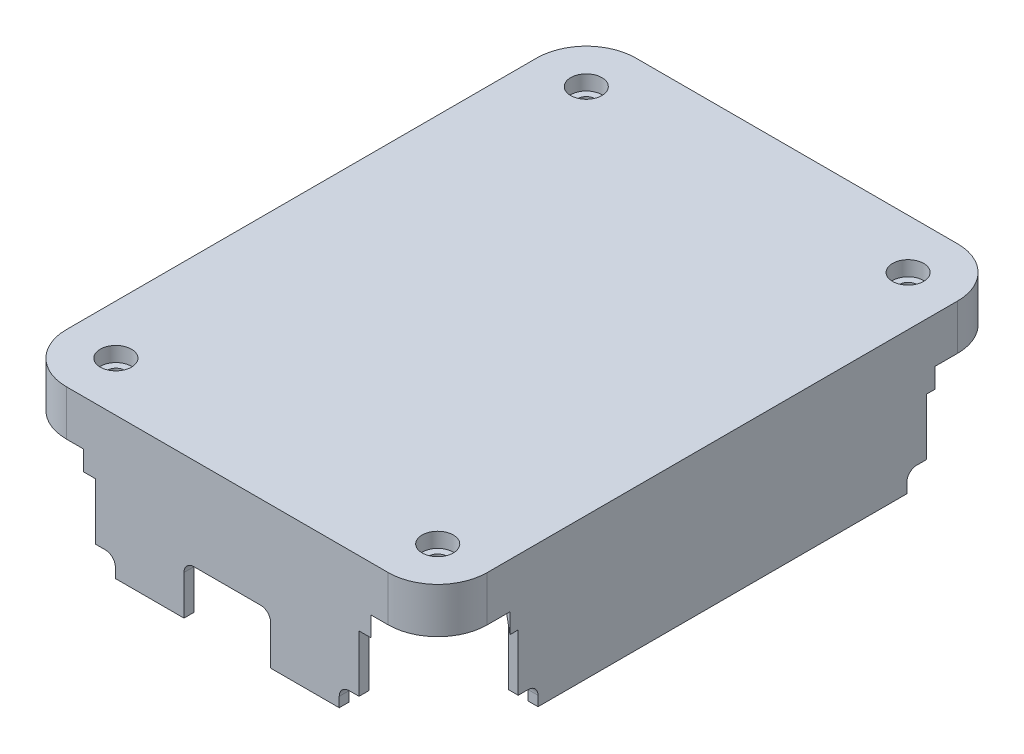
SolidWorks part; units mm, degrees
note: '?' marks a value the reader was unsure of.
material "3-D Printed ABS"
ref_plane "Front Plane" through (0, 0, 0) normal (0, 0, 1) x (1, 0, 0)
ref_plane "Top Plane" through (0, 0, 0) normal (0, 1, 0) x (1, 0, 0)
ref_plane "Right Plane" through (0, 0, 0) normal (1, 0, 0) x (0, 0, -1)
sketch "Sketch1" plane through (0, 0, 0) normal (0, 1, 0) x (1, 0, 0)
  line L1 (-53.975, -73.025) -> (53.975, -73.025)
  line L2 (-53.975, -73.025) -> (-53.975, 73.025)
  line L3 (-53.975, 73.025) -> (53.975, 73.025)
  line L4 (53.975, -73.025) -> (53.975, 73.025)
  line L5 (-53.975, -73.025) -> (53.975, 73.025) construction
  line L6 (-53.975, 73.025) -> (53.975, -73.025) construction
  point P0 (0, 0)
  dimension "D1" = 107.95
  dimension "D2" = 146.05
extrude "Boss-Extrude1" add sketch "Sketch1" against normal blind 2.54
sketch "Sketch13" plane through (0, 0, 0) normal (0, 1, 0) x (1, 0, 0)
  line L0 (0, 155.0212) -> (0, -155.0212) construction
  line L1 (0, 0) -> (-92.0171, 0) construction
  line L2 (53.975, -73.025) -> (53.975, 73.025) construction
  line L3 (53.975, -73.025) -> (28.575, -73.025)
  line L4 (53.975, -73.025) -> (53.975, -47.625)
  line L5 (53.975, -47.625) -> (28.575, -47.625)
  line L6 (28.575, -73.025) -> (28.575, -47.625)
  line L7 (-53.975, -73.025) -> (53.975, -73.025) construction
  line L8 (-28.575, -73.025) -> (-28.575, -47.625)
  line L9 (-53.975, -47.625) -> (-28.575, -47.625)
  line L10 (-53.975, -73.025) -> (-53.975, -47.625)
  line L11 (-53.975, -73.025) -> (-28.575, -73.025)
  line L12 (-53.975, 73.025) -> (-28.575, 73.025)
  line L13 (-53.975, 73.025) -> (-53.975, 47.625)
  line L14 (-53.975, 47.625) -> (-28.575, 47.625)
  line L15 (-28.575, 73.025) -> (-28.575, 47.625)
  line L16 (28.575, 73.025) -> (28.575, 47.625)
  line L17 (53.975, 47.625) -> (28.575, 47.625)
  line L18 (53.975, 73.025) -> (53.975, 47.625)
  line L19 (53.975, 73.025) -> (28.575, 73.025)
  dimension "D1" = 25.4
  dimension "D2" = 25.4
extrude "Boss-Extrude4" add sketch "Sketch13" against normal blind 16.7107
sketch "Sketch2" plane through (0, 0, 0) normal (0, 1, 0) x (1, 0, 0)
  line L0 (0, 0) -> (100.1618, 0) construction
  line L1 (0, 0) -> (0, 86.3534) construction
  line L2 (-53.975, 73.025) -> (-53.975, -73.025) construction
  line L3 (53.975, 73.025) -> (-53.975, 73.025) construction
  line L4 (0, 0) -> (-53.975, 73.025) construction
  circle A0 centre (-41.275, 60.325) radius 3.302
  circle A1 centre (41.275, 60.325) radius 3.302
  circle A2 centre (41.275, -60.325) radius 3.302
  circle A3 centre (-41.275, -60.325) radius 3.302
  dimension "D1" = 6.604
  dimension "D3" = 12.7
  dimension "D2" = 12.7
extrude "Cut-Extrude1" cut sketch "Sketch2" against normal through all
sketch "Sketch3" plane through (0, 0, 0) normal (0, 1, 0) x (1, 0, 0)
  line L0 (-53.975, 25.4) -> (53.975, 25.4) construction
  line L1 (-23.495, 60.325) -> (-19.05, 60.325)
  line L2 (-23.495, 60.325) -> (-23.495, 44.45)
  line L3 (-23.495, 44.45) -> (-19.05, 44.45)
  line L4 (-19.05, 60.325) -> (-19.05, 44.45)
  line L5 (19.05, 60.325) -> (19.05, 44.45)
  line L6 (23.495, 44.45) -> (19.05, 44.45)
  line L7 (23.495, 60.325) -> (23.495, 44.45)
  line L8 (23.495, 60.325) -> (19.05, 60.325)
  line L9 (-53.975, 73.025) -> (-53.975, -73.025) construction
  line L10 (53.975, -73.025) -> (53.975, 73.025) construction
  line L11 (0, 0) -> (0, 97.7255) construction
  line L12 (0, 50.8) -> (0, -46.9255) construction
  line L13 (23.495, -9.525) -> (19.05, -9.525)
  line L14 (23.495, -9.525) -> (23.495, 6.35)
  line L15 (23.495, 6.35) -> (19.05, 6.35)
  line L16 (19.05, -9.525) -> (19.05, 6.35)
  line L17 (-19.05, -9.525) -> (-19.05, 6.35)
  line L18 (-23.495, 6.35) -> (-19.05, 6.35)
  line L19 (-23.495, -9.525) -> (-23.495, 6.35)
  line L20 (-23.495, -9.525) -> (-19.05, -9.525)
  dimension "D1" = 15.875
  dimension "D2" = 4.445
  dimension "D3" = 19.05
  dimension "D4" = 25.4
  dimension "D5" = 44.45
extrude "Cut-Extrude2" [suppressed] cut sketch "Sketch3" against normal through all
fillet "Fillet1" radius 12.7 4 edges at (53.975, -8.3553, -73.025) (53.975, -8.3553, 73.025) (-53.975, -8.3553, 73.025) (-53.975, -8.3553, -73.025)
sketch "Sketch4" plane through (0, 0, 0) normal (0, 1, 0) x (1, 0, 0)
  line L0 (0, 0) -> (80.9727, -80.9727) construction
  line L1 (0, 0) -> (-80.9727, -80.9727) construction
  line L2 (69.1118, -51.1513) -> (28.7006, -10.7401)
  line L3 (28.7006, -10.7401) -> (10.7401, -28.7006)
  line L4 (10.7401, -28.7006) -> (51.1513, -69.1118)
  line L5 (51.1513, -69.1118) -> (69.1118, -51.1513)
  line L6 (0, 0) -> (0, -118.7381) construction
  line L7 (0, 0) -> (-98.4177, 0) construction
  line L8 (-51.1513, -69.1118) -> (-69.1118, -51.1513)
  line L9 (-69.1118, -51.1513) -> (-28.7006, -10.7401)
  line L10 (-28.7006, -10.7401) -> (-10.7401, -28.7006)
  line L11 (-10.7401, -28.7006) -> (-51.1513, -69.1118)
  line L12 (-69.1118, 51.1513) -> (-28.7006, 10.7401)
  line L13 (-51.1513, 69.1118) -> (-69.1118, 51.1513)
  line L14 (-10.7401, 28.7006) -> (-51.1513, 69.1118)
  line L15 (-28.7006, 10.7401) -> (-10.7401, 28.7006)
  line L16 (51.1513, 69.1118) -> (69.1118, 51.1513)
  line L17 (69.1118, 51.1513) -> (28.7006, 10.7401)
  line L18 (28.7006, 10.7401) -> (10.7401, 28.7006)
  line L19 (10.7401, 28.7006) -> (51.1513, 69.1118)
  point P6 (19.7204, -19.7204)
  dimension "D1" = 25.4
  dimension "D2" = 57.15
  dimension "D3" = 45
extrude "Cut-Extrude3" [suppressed] cut sketch "Sketch4" against normal blind 1.5875
sketch "Sketch6" [suppressed] plane through (0, 0, 0) normal (0, 1, 0) x (1, 0, 0)
  line L0 (46.3377, -44.1074) -> (34.6634, -32.4331) construction
  line L1 (0, 0) -> (0, -117.7376) construction
  line L2 (0, 0) -> (-151.7285, 0) construction
  line L4 (28.1601, -10.1996) -> (10.1996, -28.1601) construction
  line L5 (50.6107, -68.5712) -> (68.5712, -50.6107) construction
  text T0 "ESC" font "Century Gothic" height in points 22
  dimension "D1" = 45
  dimension "D2" = 20.32
  dimension "D3" = 20.32
extrude "Cut-Extrude5" [suppressed] cut sketch "Sketch6" against normal blind 3.175
sketch "Sketch5" plane through (0, 0, 0) normal (0, 1, 0) x (1, 0, 0)
  line L0 (41.275, 73.025) -> (-41.275, 73.025) construction
  line L1 (14.2875, 15.875) -> (-14.2875, 15.875)
  line L2 (14.2875, 15.875) -> (14.2875, 66.675)
  line L3 (14.2875, 66.675) -> (-14.2875, 66.675)
  line L4 (-14.2875, 15.875) -> (-14.2875, 66.675)
  point P4 (0, 15.875)
  dimension "D1" = 50.8
  dimension "D2" = 28.575
  dimension "D3" = 6.35
extrude "Cut-Extrude4" [suppressed] cut sketch "Sketch5" against normal blind 1.5875
ref_axis "Axis1" through (0, 0.3175, 0) along (0, -1, 0)?
pattern_circular "CirPattern1" [suppressed] count 4 over 360 about axis through (0, 0.3175, 0) along (0, -1, 0)
sketch "Sketch7" plane through (0, 0, 0) normal (0, 1, 0) x (1, 0, 0)
  line L0 (0, 0) -> (0, -54.962) construction
  line L1 (63.4018, -13.3522) -> (38.0018, -13.3522)
  line L2 (63.4018, -13.3522) -> (63.4018, 43.7978)
  line L3 (63.4018, 43.7978) -> (38.0018, 43.7978)
  line L4 (38.0018, -13.3522) -> (38.0018, 43.7978)
  line L5 (-38.0018, -13.3522) -> (-38.0018, 43.7978)
  line L6 (-63.4018, 43.7978) -> (-38.0018, 43.7978)
  line L7 (-63.4018, -13.3522) -> (-63.4018, 43.7978)
  line L8 (-63.4018, -13.3522) -> (-38.0018, -13.3522)
  line L9 (-41.275, -73.025) -> (41.275, -73.025) construction
  line L10 (38.5677, -40.64) -> (-18.5823, -40.64)
  line L11 (38.5677, -40.64) -> (38.5677, -66.04)
  line L12 (38.5677, -66.04) -> (-18.5823, -66.04)
  line L13 (-18.5823, -40.64) -> (-18.5823, -66.04)
  line L14 (38.5677, -40.64) -> (-18.5823, -66.04) construction
  line L15 (38.5677, -66.04) -> (-18.5823, -40.64) construction
  line L16 (19.844, -36.1003) -> (-37.306, -36.1003)
  line L17 (19.844, -36.1003) -> (19.844, -61.5003)
  line L18 (19.844, -61.5003) -> (-37.306, -61.5003)
  line L19 (-37.306, -36.1003) -> (-37.306, -61.5003)
  line L20 (19.844, -36.1003) -> (-37.306, -61.5003) construction
  line L21 (19.844, -61.5003) -> (-37.306, -36.1003) construction
  point P11 (9.9927, -53.34)
  point P18 (-8.731, -48.8003)
  dimension "D1" = 57.15
  dimension "D2" = 25.4
  dimension "D3" = 57.15
  dimension "D4" = 25.4
  dimension "D5" = 6.985
  dimension "D6" = 57.15
  dimension "D7" = 25.4
extrude "Cut-Extrude6" [suppressed] cut sketch "Sketch7" against normal blind 1.27
sketch "Sketch8" plane through (0, 0, 0) normal (0, 1, 0) x (1, 0, 0)
  line L7 (19.05, -31.75) -> (-19.05, -31.75)
  line L8 (19.05, -31.75) -> (19.05, 31.75)
  line L9 (19.05, 31.75) -> (-19.05, 31.75)
  line L10 (-19.05, -31.75) -> (-19.05, 31.75)
  point P0 (0, 0)
  dimension "D1" = 38.1
  dimension "D2" = 31.75
  dimension "D3" = 63.5
extrude "Boss-Extrude3" [suppressed] add sketch "Sketch8" along normal blind 2.54
sketch "Sketch11" plane through (0, 0, 0) normal (0, 1, 0) x (1, 0, 0)
  line L1 (19.05, -9.525) -> (-19.05, -9.525)
  line L2 (19.05, -9.525) -> (19.05, 6.35)
  line L3 (19.05, 6.35) -> (-19.05, 6.35)
  line L4 (-19.05, -9.525) -> (-19.05, 6.35)
extrude "Cut-Extrude9" [suppressed] cut sketch "Sketch11" against normal mid plane 2.54
sketch "Sketch12" [suppressed] plane through (0, 0, 0) normal (0, 1, 0) x (1, 0, 0)
  line L0 (-23.495, -9.525) -> (-19.05, -9.525) construction
  line L1 (12.7, -9.525) -> (-12.7, -9.525)
  line L2 (12.7, -9.525) -> (12.7, 6.35)
  line L3 (12.7, 6.35) -> (-12.7, 6.35)
  line L4 (-12.7, -9.525) -> (-12.7, 6.35)
  line L5 (-19.05, 6.35) -> (-23.495, 6.35) construction
  line L6 (19.05, 52.3875) -> (-19.05, 52.3875) construction
  line L7 (19.05, 60.325) -> (19.05, 44.45) construction
  line L8 (-19.05, 44.45) -> (-19.05, 60.325) construction
  line L9 (-12.7, 114.3) -> (-12.7, 98.425)
  line L10 (12.7, 98.425) -> (-12.7, 98.425)
  line L11 (12.7, 114.3) -> (12.7, 98.425)
  line L12 (12.7, 114.3) -> (-12.7, 114.3)
  point P8 (0, -9.525)
  dimension "D1" = 25.4
extrude "Cut-Extrude12" [suppressed] cut sketch "Sketch12" along normal through all
sketch "Sketch9" plane through (0, 0, 0) normal (0, 1, 0) x (1, 0, 0)
  line L1 (25.1579, -52.4084) -> (-25.6421, -52.4084)
  line L2 (25.1579, -52.4084) -> (25.1579, -1.6084)
  line L3 (25.1579, -1.6084) -> (-25.6421, -1.6084)
  line L4 (-25.6421, -52.4084) -> (-25.6421, -1.6084)
  line L5 (25.1579, -52.4084) -> (-25.6421, -1.6084) construction
  line L6 (25.1579, -1.6084) -> (-25.6421, -52.4084) construction
  point P0 (-0.2421, -27.0084)
  dimension "D1" = 50.8
  dimension "D2" = 50.8
fillet "Fillet2" [suppressed] radius 12.7
sketch "Sketch14" plane through (0, -16.7107, 0) normal (0, -1, 0) x (1, 0, 0)
  line L0 (0, 0) -> (0, -152.4) construction
  line L1 (0, 0) -> (152.4, 0) construction
  line L2 (0, 0) -> (152.4, -152.4) construction
  line L3 (152.4, -152.4) -> (41.275, -60.325) construction
  line L4 (41.275, -60.325) -> (28.7776, -49.97) construction
  line L5 (28.7776, -49.97) -> (0, -26.1257) construction
  line L6 (22.4276, -28.3459) -> (6.35, -47.7499)
  line L7 (6.35, -47.7499) -> (138.4692, -157.2201)
  line L8 (138.4692, -157.2201) -> (154.5468, -137.816)
  line L9 (154.5468, -137.816) -> (22.4276, -28.3459)
  line L10 (-22.4276, -28.3459) -> (-6.35, -47.7499)
  line L11 (-154.5468, -137.816) -> (-22.4276, -28.3459)
  line L12 (-6.35, -47.7499) -> (-138.4692, -157.2201)
  line L13 (-138.4692, -157.2201) -> (-154.5468, -137.816)
  line L14 (-154.5468, 137.816) -> (-22.4276, 28.3459)
  line L15 (-138.4692, 157.2201) -> (-154.5468, 137.816)
  line L16 (-6.35, 47.7499) -> (-138.4692, 157.2201)
  line L17 (-22.4276, 28.3459) -> (-6.35, 47.7499)
  line L18 (22.4276, 28.3459) -> (6.35, 47.7499)
  line L19 (138.4692, 157.2201) -> (154.5468, 137.816)
  line L20 (154.5468, 137.816) -> (22.4276, 28.3459)
  line L21 (6.35, 47.7499) -> (138.4692, 157.2201)
  point P3 (14.3888, -38.0479)
  point P6 (41.275, -60.325)
  dimension "D1" = 152.4
  dimension "D2" = 152.4
  dimension "D3" = 6.35
  dimension "D4" = 12.5997
extrude "Cut-Extrude13" cut sketch "Sketch14" against normal blind 5.08
sketch "Sketch15" plane through (0, 0, 0) normal (0, 1, 0) x (1, 0, 0)
  line L0 (0, 0) -> (72.5178, 0) construction
  line L1 (0, 0) -> (0, 124.598) construction
  circle A0 centre (-41.275, 60.325) radius 6.35
  circle A1 centre (41.275, 60.325) radius 6.35
  circle A2 centre (-41.275, -60.325) radius 6.35
  circle A3 centre (41.275, -60.325) radius 6.35
extrude "Boss-Extrude5" add sketch "Sketch15" against normal offset from surface (9.0907 mm away) 2.54 up to face at (-41.6508, -11.6307, -60.7008)
hole_wizard "M4 Clearance Hole1" [suppressed] positions "Sketch18" profile "Sketch16" hole size "M4" standard "ANSI Metric"
sketch "Sketch18" plane through (0, -19.05, 0) normal (0, -1, 0) x (-1, 0, 0)
  point P0 (41.275, 60.325)
  point P3 (41.275, -60.325)
  point P6 (-41.275, -60.325)
  point P9 (-41.275, 60.325)
sketch "Sketch16" plane through (-41.275, -19.05, -60.325) normal (1, 0, 0) x (0, 0, -1)
  line L0 (0, 0) -> (0, 19.05)
  line L1 (0, 19.05) -> (2.25, 19.05)
  line L2 (2.25, 19.05) -> (2.25, 0)
  line L5 (2.25, 0) -> (0, 0)
  line L11 (0, -6.35) -> (0, 107.95) construction
  dimension "Thru Hole Dia." = 4.5
  dimension "Thru Hole Depth" = 19.05
hole_wizard "CBORE for M4 SHCS1" [suppressed] positions "Sketch21" profile "Sketch20" counterbore size "M4" standard "ANSI Metric"
sketch "Sketch21" [suppressed] plane through (0, 0, 0) normal (0, 1, 0) x (1, 0, 0)
  point P0 (41.275, 60.325)
  point P3 (-41.275, 60.325)
  point P6 (-41.275, -60.325)
  point P9 (41.275, -60.325)
sketch "Sketch20" plane through (41.275, 0, -60.325) normal (1, 0, 0) x (0, 0, 1)
  line L0 (0, 0) -> (0, 24.13)
  line L1 (0, 24.13) -> (2.25, 24.13)
  line L3 (2.25, 24.13) -> (2.25, 4)
  line L4 (2.25, 4) -> (4, 4)
  line L5 (4, 4) -> (4, 0)
  line L7 (4, 0) -> (0, 0)
  line L11 (0, -6.35) -> (0, 107.95) construction
  dimension "Thru Hole Dia." = 4.5
  dimension "Thru Hole Depth" = 24.13
  dimension "C'Bore Dia." = 8
  dimension "C'Bore Depth" = 4
sketch "Sketch23" plane through (0, -11.6307, 0) normal (0, -1, 0) x (1, 0, 0)
  circle A0 centre (-41.275, -60.325) radius 2.25
  dimension "D1" = 4.5
extrude "Cut-Extrude14" cut sketch "Sketch23" against normal through all
sketch "Sketch24" plane through (0, 0, 0) normal (0, 1, 0) x (1, 0, 0)
  circle A0 centre (-41.275, 60.325) radius 4
  dimension "D1" = 8
extrude "Cut-Extrude15" cut sketch "Sketch24" against normal blind 3.81
mirror "Mirror1" about plane through (0, 0, 0) normal (0, 0, 1) of "Cut-Extrude15", "Cut-Extrude14"
mirror "Mirror2" about plane through (0, 0, 0) normal (1, 0, 0) of "Cut-Extrude15", "Cut-Extrude14", "Mirror1"
fillet "Fillet3" radius 12.7 4 edges at (-28.575, -7.0853, -47.625) (28.575, -7.0853, -47.625) (28.575, -7.0853, 47.625) (-28.575, -7.0853, 47.625)
sketch "Sketch25" plane through (0, 0, 0) normal (0, 1, 0) x (1, 0, 0)
  line L0 (0, 0) -> (0, -33.9706) construction
  line L1 (0, 0) -> (63.8751, 0) construction
  circle A0 centre (30.0609, 0) radius 3.4925
  circle A1 centre (30.0609, -24.9682) radius 3.4925
  circle A2 centre (30.0609, 24.9682) radius 3.4925
  circle A3 centre (-30.0609, 24.9682) radius 3.4925
  circle A4 centre (-30.0609, -24.9682) radius 3.4925
  circle A5 centre (-30.0609, 0) radius 3.4925
  dimension "D1" = 6.985
  dimension "D2" = 6.985
  dimension "D3" = 24.9682
  dimension "D4" = 30.0609
extrude "GimbalMount1" [suppressed] cut sketch "Sketch25" against normal through all
sketch "Sketch26" [suppressed] plane through (0, 0, 0) normal (0, 1, 0) x (1, 0, 0)
  circle A0 centre (30.0609, -24.9682) radius 5.715
  circle A1 centre (30.0609, 0) radius 5.715
  circle A2 centre (30.0609, 24.9682) radius 5.715
  circle A3 centre (-30.0609, -24.9682) radius 5.715
  circle A4 centre (-30.0609, 0) radius 5.715
  circle A5 centre (-30.0609, 24.9682) radius 5.715
  dimension "D1" = 11.43
extrude "GimbalMount2" [suppressed] cut sketch "Sketch26" against normal blind 1.524
fillet "Fillet4" radius 1.016 4 edges at (41.275, -11.6307, 63.627) (-41.275, -11.6307, 57.023) (-41.275, -11.6307, -57.023) (41.275, -11.6307, -63.627)
sketch "Sketch27" plane through (0, -2.54, 0) normal (0, -1, 0) x (1, 0, 0)
  line L1 (33.7889, -73.025) -> (-33.7889, -73.025)
  line L2 (33.7889, -73.025) -> (33.7889, -70.485)
  line L3 (33.7889, -70.485) -> (-33.7889, -70.485)
  line L4 (-33.7889, -73.025) -> (-33.7889, -70.485)
  line L6 (0, 0) -> (0, -45.0707) construction
  line L7 (0, 0) -> (-77.1364, 0) construction
  line L8 (-33.7889, 73.025) -> (-33.7889, 70.485)
  line L9 (33.7889, 70.485) -> (-33.7889, 70.485)
  line L10 (33.7889, 73.025) -> (33.7889, 70.485)
  line L11 (33.7889, 73.025) -> (-33.7889, 73.025)
  line L13 (53.975, -52.3805) -> (51.435, -52.3805)
  line L14 (53.975, -52.3805) -> (53.975, 52.3805)
  line L15 (53.975, 52.3805) -> (51.435, 52.3805)
  line L16 (51.435, -52.3805) -> (51.435, 52.3805)
  line L17 (-51.435, -52.3805) -> (-51.435, 52.3805)
  line L18 (-53.975, 52.3805) -> (-51.435, 52.3805)
  line L19 (-53.975, -52.3805) -> (-53.975, 52.3805)
  line L20 (-53.975, -52.3805) -> (-51.435, -52.3805)
  line L22 (28.575, -66.1649) -> (36.8544, -73.025) construction
  line L23 (-36.8544, -73.025) -> (-28.575, -66.1649) construction
  line L24 (28.575, -73.025) -> (-28.575, -73.025) construction
  line L25 (53.975, -54.4851) -> (45.6956, -47.625) construction
  line L26 (53.975, 47.625) -> (53.975, -47.625) construction
  line L27 (45.6956, 47.625) -> (53.975, 54.4851) construction
  dimension "D1" = 2.54
  dimension "D2" = 2.54
extrude "Boss-Extrude6" add sketch "Sketch27" along normal blind 33.782
sketch "Sketch28" plane through (0, 0, -73.025) normal (0, 0, -1) x (-1, 0, 0)
  line L0 (-41.275, 0) -> (41.275, 0) construction
  line L1 (-17.526, -36.322) -> (17.526, -36.322)
  line L2 (-16.891, -28.702) -> (-16.891, -21.3995)
  line L3 (-14.351, -18.8595) -> (14.351, -18.8595)
  line L4 (16.891, -28.702) -> (16.891, -21.3995)
  line L5 (33.7889, -36.322) -> (-33.7889, -36.322) construction
  line L6 (19.431, -31.242) -> (27.051, -31.242)
  line L7 (0, -18.8595) -> (0, 0) construction
  line L8 (17.526, -36.322) -> (29.591, -36.322)
  line L9 (29.591, -33.782) -> (29.591, -36.322)
  line L11 (-19.431, -31.242) -> (-27.051, -31.242)
  line L13 (-17.526, -36.322) -> (-29.591, -36.322)
  line L14 (-29.591, -33.782) -> (-29.591, -36.322)
  arc A0 (-29.591, -33.782) -> (-27.051, -31.242) centre (-27.051, -33.782) cw
  arc A1 (-19.431, -31.242) -> (-16.891, -28.702) centre (-19.431, -28.702) ccw
  arc A2 (-16.891, -21.3995) -> (-14.351, -18.8595) centre (-14.351, -21.3995) cw
  arc A3 (14.351, -18.8595) -> (16.891, -21.3995) centre (14.351, -21.3995) cw
  arc A4 (16.891, -28.702) -> (19.431, -31.242) centre (19.431, -28.702) ccw
  arc A5 (27.051, -31.242) -> (29.591, -33.782) centre (27.051, -33.782) cw
  point P5 (0, -36.322)
  point P19 (-29.591, -31.242)
  point P25 (-16.891, -18.8595)
  point P28 (16.891, -18.8595)
  point P34 (29.591, -31.242)
  dimension "D7" = 2.54
  dimension "D1" = 17.4625
  dimension "D2" = 33.782
  dimension "D3" = 10.16
  dimension "D4" = 5.08
  dimension "D5" = 10.16
  dimension "D6" = 5.08
extrude "Cut-Extrude16" cut sketch "Sketch28" against normal blind 41.656
sketch "Sketch29" plane through (-53.975, 0, 0) normal (-1, 0, 0) x (0, 0, 1)
  line L0 (0, -36.322) -> (0, -17.4257) construction
  line L1 (-52.3805, -36.322) -> (-47.3005, -36.322)
  line L2 (-52.3805, -36.322) -> (-52.3805, -31.242)
  line L3 (-52.3805, -31.242) -> (-49.8405, -31.242)
  line L4 (-47.3005, -36.322) -> (-47.3005, -33.782)
  line L5 (52.3805, -36.322) -> (-52.3805, -36.322) construction
  line L6 (47.3005, -36.322) -> (47.3005, -33.782)
  line L7 (52.3805, -31.242) -> (49.8405, -31.242)
  line L8 (52.3805, -36.322) -> (52.3805, -31.242)
  line L9 (52.3805, -36.322) -> (47.3005, -36.322)
  arc A0 (-47.3005, -33.782) -> (-49.8405, -31.242) centre (-49.8405, -33.782) ccw
  arc A1 (47.3005, -33.782) -> (49.8405, -31.242) centre (49.8405, -33.782) cw
  dimension "D1" = 2.54
  dimension "D2" = 5.08
  dimension "D3" = 5.08
extrude "Cut-Extrude17" cut sketch "Sketch29" against normal through all
sketch "Sketch30" plane through (0, 0, 73.025) normal (0, 0, 1) x (1, 0, 0)
  line L0 (0, -36.322) -> (0, -22.969) construction
  line L1 (-33.7889, -36.322) -> (-28.7089, -36.322)
  line L2 (-33.7889, -36.322) -> (-33.7889, -31.242)
  line L3 (-33.7889, -31.242) -> (-31.2489, -31.242)
  line L4 (-28.7089, -36.322) -> (-28.7089, -33.782)
  line L5 (33.7889, -36.322) -> (-33.7889, -36.322) construction
  line L6 (28.7089, -36.322) -> (28.7089, -33.782)
  line L7 (33.7889, -31.242) -> (31.2489, -31.242)
  line L8 (33.7889, -36.322) -> (33.7889, -31.242)
  line L9 (33.7889, -36.322) -> (28.7089, -36.322)
  arc A0 (-28.7089, -33.782) -> (-31.2489, -31.242) centre (-31.2489, -33.782) ccw
  arc A1 (28.7089, -33.782) -> (31.2489, -31.242) centre (31.2489, -33.782) cw
  dimension "D1" = 2.54
  dimension "D2" = 5.08
  dimension "D3" = 5.08
extrude "Cut-Extrude18" cut sketch "Sketch30" against normal through all
sketch "Sketch31" plane through (0, 0, 73.025) normal (0, 0, 1) x (1, 0, 0)
  line L0 (28.7089, -36.322) -> (-28.7089, -36.322) construction
  line L1 (-11.1125, -36.322) -> (11.1125, -36.322)
  line L2 (-11.1125, -36.322) -> (-11.1125, -23.622)
  line L3 (-11.1125, -23.622) -> (11.1125, -23.622)
  line L4 (11.1125, -36.322) -> (11.1125, -23.622)
  line L5 (0, -23.622) -> (0, -15.4197) construction
  line L6 (-41.275, 0) -> (41.275, 0) construction
  point P10 (0, 0)
  dimension "D1" = 12.7
  dimension "D2" = 22.225
extrude "Cut-Extrude19" cut sketch "Sketch31" against normal up to next
fillet "Fillet5" radius 2.54 2 edges at (11.1125, -23.622, 71.755) (-11.1125, -23.622, 71.755)
equation "\"Plate Thickness\"= \"Plate Thickness@Quad Assemb.sldasm\""
equation "\"D1@Boss-Extrude1\"=\"Plate Thickness\""
equation "\"Plate Dim X\"= \"Plate Dim X@Quad Assemb.sldasm\""
equation "\"Plate Dim Y\"= \"Plate Dim Y@Quad Assemb.sldasm\""
equation "\"D1@Boss-Extrude4\"=\"Component Y@Quad Assemb.sldasm\"-\"ArmBase@Arm V3-1.Part\""
equation "\"D4@Sketch14\"=\"ArmBase@Arm V3-1.Part\"/2+.005"
equation "\"Dowell Width\"= \"Dowell Width@Quad Assemb.sldasm\""
equation "\"D1@Sketch2\"=\"Dowell Width\"+.01"
equation "\"Dowell Height\"= \"Dowell Height@Quad Assemb.sldasm\""
equation "\"D1@Boss-Extrude5\"=\"Dowell Height\""
equation "\"GimbalMount1\"= if ( \"Gimbal Mount@Quad Assemb.sldasm\" = 1 , \"unsuppressed\" , \"suppressed\" )"
equation "\"GimbalMount2\"= if ( \"Gimbal Mount@Quad Assemb.sldasm\" = 1 , \"unsuppressed\" , \"suppressed\" )"
equation "\"D1@Boss-Extrude6\"=\"Component Y@Quad Assemb.sldasm\"-.31"
equation "\"D1@Sketch28\"=\"radio rx Z@Quad Assemb.sldasm\"+3/16"
equation "\"D2@Sketch28\"=\"radio rx x@quad assemb.sldasm\"+.2"
